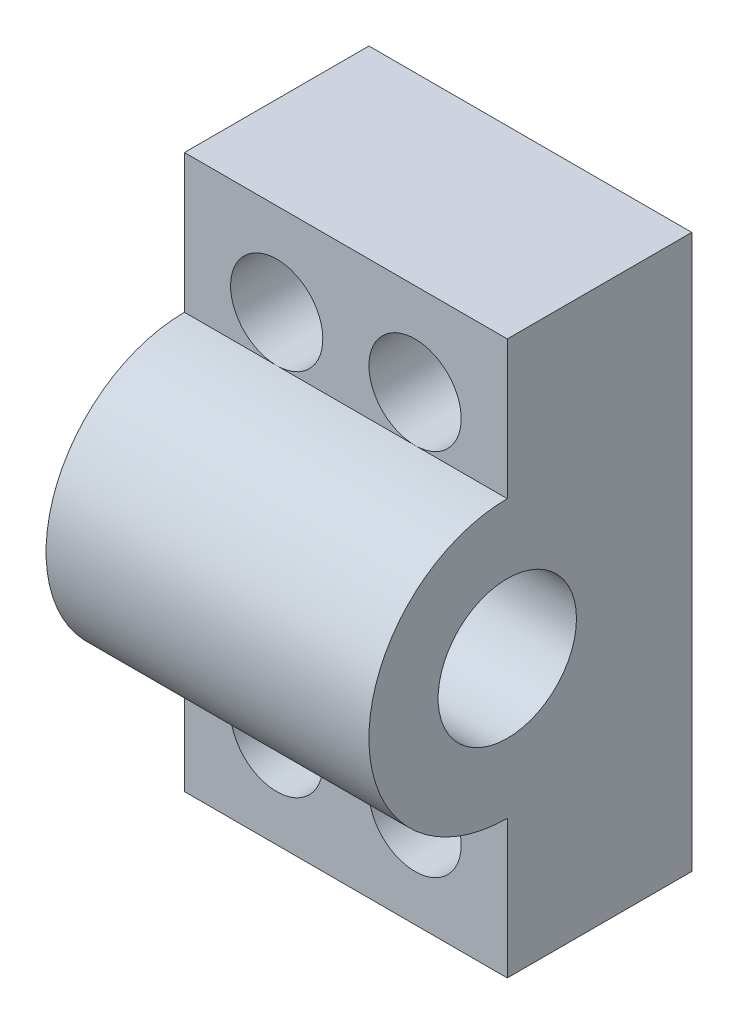
SolidWorks part; units mm, degrees
ref_plane "Front Plane" through (0, 0, 0) normal (0, 0, 1) x (1, 0, 0)
ref_plane "Top Plane" through (0, 0, 0) normal (0, 1, 0) x (1, 0, 0)
ref_plane "Right Plane" through (0, 0, 0) normal (1, 0, 0) x (0, 0, -1)
sketch "Sketch1" plane through (0, 0, 0) normal (1, 0, 0) x (0, 0, -1)
  line L0 (0, -30) -> (0, 30)
  line L1 (0, 30) -> (-20, 30)
  line L2 (-20, 30) -> (-20, 15)
  line L3 (-20, -15) -> (-20, -30)
  line L4 (-20, -30) -> (0, -30)
  line L5 (0, 0) -> (-35, 0) construction
  arc A0 (-20, 15) -> (-20, -15) centre (-20, 0) ccw
  point P0 (0, 0)
  dimension "D1" = 15
  dimension "D2" = 20
  dimension "D3" = 60
extrude "body" add sketch "Sketch1" along normal blind 35
sketch "Sketch2" plane through (0, 0, 0) normal (0, 0, 1) x (1, 0, 0)
  line L0 (0, 0) -> (35, 0) construction
  line L1 (0, 15) -> (0, -15) construction
  line L2 (35, -15) -> (35, 15) construction
  line L3 (17.5, -30) -> (17.5, 30) construction
  line L4 (35, -30) -> (0, -30) construction
  line L5 (35, 30) -> (0, 30) construction
  circle A0 centre (10, 20) radius 5
  circle A1 centre (25, 20) radius 5
  circle A2 centre (10, -20) radius 5
  circle A3 centre (25, -20) radius 5
  dimension "D1" = 10
  dimension "D3" = 15
  dimension "D2" = 20
extrude "fixing holes" cut sketch "Sketch2" along normal through all
sketch "Sketch3" plane through (35, 0, 0) normal (1, 0, 0) x (0, 0, -1)
  circle A0 centre (-20, 0) radius 7.5
  arc A2 (-20, 15) -> (-20, -15) centre (-20, 0) ccw construction
  dimension "D1" = 15
extrude "shaft hole" cut sketch "Sketch3" against normal blind 40
